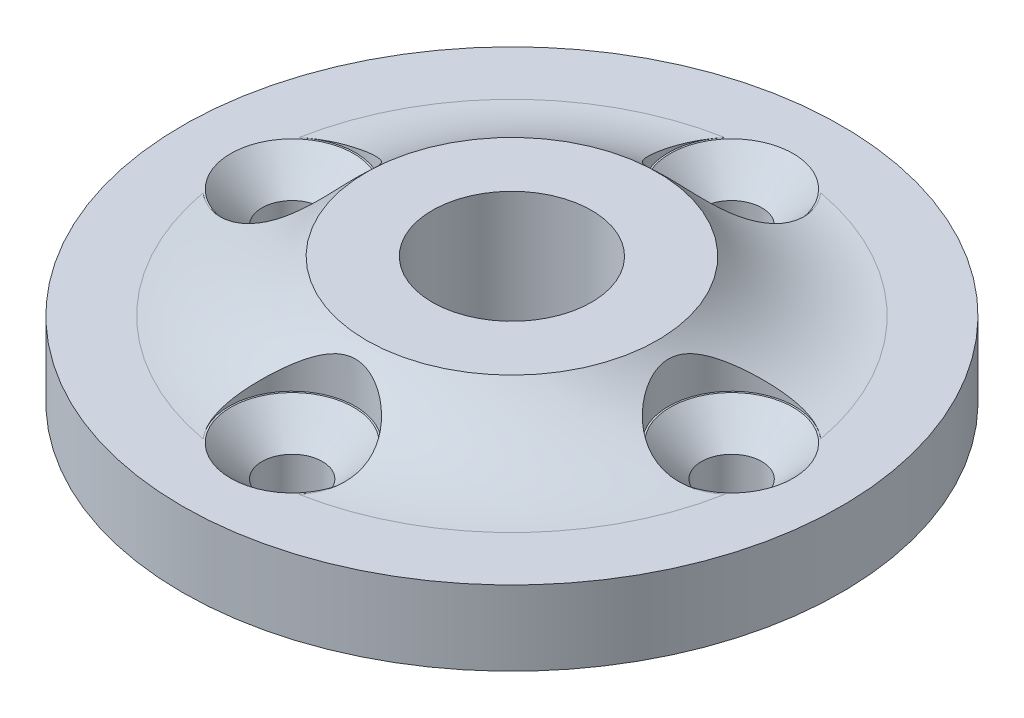
SolidWorks part; units mm, degrees
ref_plane "Alzado" through (0, 0, 0) normal (0, 0, 1) x (1, 0, 0)
ref_plane "Planta" through (0, 0, 0) normal (0, 1, 0) x (1, 0, 0)
ref_plane "Vista lateral" through (0, 0, 0) normal (1, 0, 0) x (0, 0, -1)
sketch "Sketch1" plane through (0, 0, 0) normal (0, 1, 0) x (1, 0, 0)
  circle A0 centre (0, 0) radius 30
  circle A1 centre (0, 0) radius 20 construction
  circle A2 centre (0, 0) radius 7.25 construction
  dimension "D1" = 60
  dimension "D2" = 40
  dimension "D3" = 14.5
sketch "Sketch2" plane through (0, 0, 0) normal (0, 1, 0) x (1, 0, 0)
  circle A0 centre (0, 0) radius 30
  circle A1 centre (0, 0) radius 30 construction
extrude "Boss-Extrude1" add sketch "Sketch2" along normal blind 6.8
sketch "Sketch3" plane through (0, 6.8, 0) normal (0, 1, 0) x (1, 0, 0)
  circle A0 centre (0, 0) radius 7.25
  circle A1 centre (0, 0) radius 13.25
  dimension "D1" = 6
  dimension "D2" = 14.5
extrude "Boss-Extrude2" add sketch "Sketch3" along normal blind 4.7
fillet "Fillet1" radius 15 1 edges at (0, 6.8, 13.25)
sketch "Sketch5" plane through (0, 11.5, 0) normal (0, 1, 0) x (1, 0, 0)
  circle A0 centre (0, 20) radius 3
  circle A1 centre (0, 0) radius 20 construction
  dimension "D1" = 6
hole_wizard "CSK for M5 Hex Socket Countersunk Cap Screw1" positions "Sketch8" profile "Sketch9" countersink size "M5" standard "ISO" end condition through all
sketch "Sketch8" plane through (0, 6.8, 0) normal (0, 1, 0) x (1, 0, 0)
  point P0 (0, 20)
sketch "Sketch9" plane through (0, 6.8, -20) normal (1, 0, 0) x (0, 0, 1)
  line L0 (0, 0) -> (0, 6.8)
  line L1 (0, 6.8) -> (2.75, 6.8)
  line L2 (2.75, 6.8) -> (2.75, 2.85)
  line L3 (2.75, 2.85) -> (5.6, 0)
  line L5 (5.6, 0) -> (0, 0)
  line L6 (-2.75, 2.85) -> (-5.6, 0) construction
  line L11 (0, -6.35) -> (0, 107.95) construction
  dimension "Thru Hole Dia." = 5.5
  dimension "Thru Hole Depth" = 6.8
  dimension "Near C'Sink Dia." = 11.2
  dimension "Near C'Sink Angle" = 90
sketch "Sketch6" plane through (0, 11.5, 0) normal (0, 1, 0) x (1, 0, 0)
  circle A0 centre (0, 20) radius 5.75
  dimension "D1" = 11.5
extrude "Cut-Extrude3" cut sketch "Sketch6" against normal up to surface (4.7 mm away) up to face at (0, 6.8, -0.7227)
pattern_circular "CirPattern1" count 4 over 360 about axis through (0, 11.5, 0) along (0, 1, 0) of "Cut-Extrude3", "CSK for M5 Hex Socket Countersunk Cap Screw1"
sketch "Sketch7" plane through (0, 11.5, 0) normal (0, 1, 0) x (1, 0, 0)
  circle A0 centre (0, 0) radius 7.25 construction
  circle A1 centre (0, 0) radius 7.25
extrude "Cut-Extrude4" cut sketch "Sketch7" against normal through all
